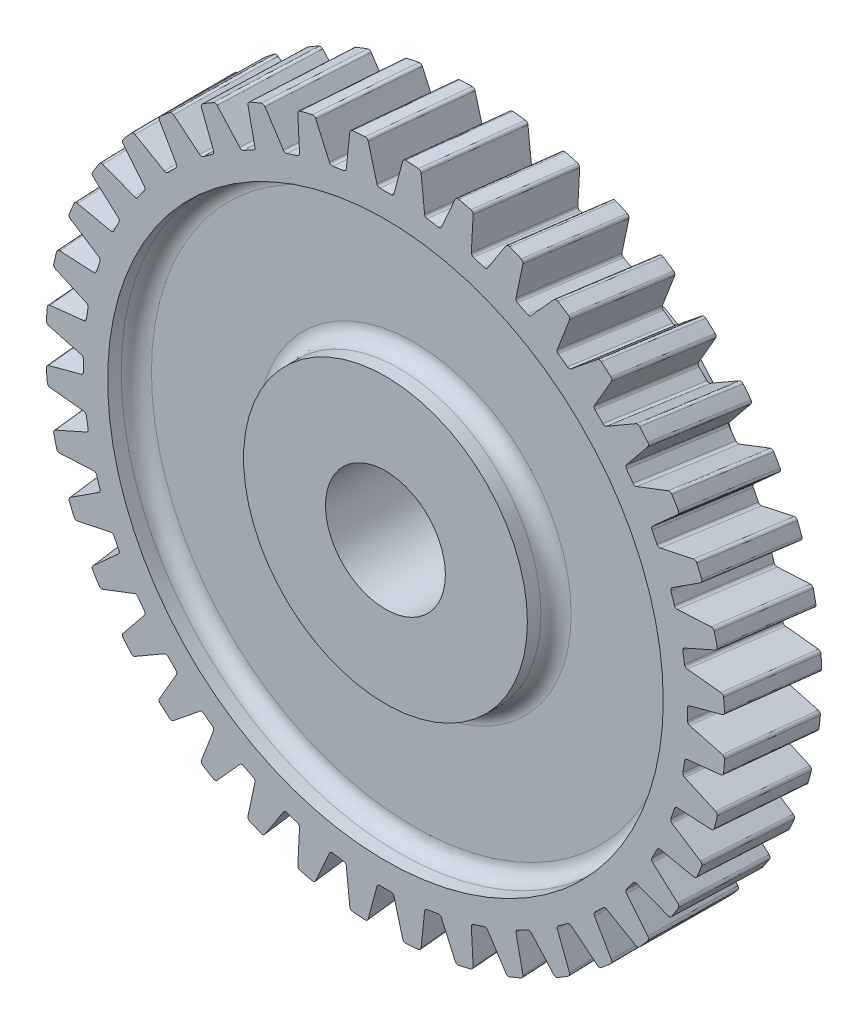
SolidWorks part; units mm, degrees
ref_plane "Front Plane" through (0, 0, 0) normal (0, 0, 1) x (1, 0, 0)
ref_plane "Top Plane" through (0, 0, 0) normal (0, 1, 0) x (1, 0, 0)
ref_plane "Right Plane" through (0, 0, 0) normal (1, 0, 0) x (0, 0, -1)
sketch "Sketch2" plane through (0, 0, 0) normal (1, 0, 0) x (0, 0, -1)
  line L0 (0, 0) -> (0, 22.5) construction
  line L1 (11, 3.9688) -> (-3.2, 3.9687)
  line L2 (-3.2, 3.9687) -> (-3.2, 9.4)
  line L3 (-3.2, 9.4) -> (-1.3, 9.4)
  line L4 (-1.3, 9.4) -> (-1.3, 18.4)
  line L5 (-1.3, 18.4) -> (-3.2, 18.4)
  line L6 (-3.2, 18.4) -> (-3.2, 22.5)
  line L7 (-3.2, 22.5) -> (3.2, 22.5)
  line L8 (3.2, 18.4) -> (3.2, 22.5)
  line L9 (1.3, 18.4) -> (3.2, 18.4)
  line L10 (1.3, 9.4) -> (1.3, 18.4)
  line L11 (3.2, 9.4) -> (1.3, 9.4)
  line L12 (3.2, 9.4) -> (11, 9.4)
  line L13 (11, 9.4) -> (11, 3.9688)
  line L14 (0, 0) -> (14.174, 0) construction
  dimension "D1" = 14.2
  dimension "D2" = 3.2
  dimension "D3" = 4.5
  dimension "D4" = 7.9375
  dimension "D5" = 9.4
  dimension "D6" = 9
  dimension "D7" = 22.5
  dimension "D8" = 6.4
revolve "Revolve1" add sketch "Sketch2" angle 360 about L14
fillet "Fillet1" radius 1 4 edges at (18.4, 0, 1.3) (9.4, 0, 1.3) (9.4, 0, -1.3) (18.4, 0, -1.3)
sketch "Sketch3" plane through (0, 0, 3.2) normal (0, 0, 1) x (1, 0, 0)
  line L0 (0, 22.6922) -> (0, 20) construction
  line L1 (-0.525, 20) -> (0.525, 20)
  line L2 (0.525, 20) -> (1.2464, 22.6922)
  line L3 (1.2464, 22.6922) -> (-1.2464, 22.6922)
  line L4 (-0.525, 20) -> (-1.2464, 22.6922)
  dimension "D1" = 20
  dimension "D2" = 1.05
  dimension "D3" = 15
  dimension "D4" = 2.4927
sketch "Sketch4" plane through (0, 0, 0) normal (0, 1, 0) x (1, 0, 0)
  line L0 (0, -3.2) -> (0.691, 3.2)
  line L1 (1.2464, -3.2) -> (-1.2464, -3.2) construction
  line L2 (22.5, 3.2) -> (-22.5, 3.2) construction
  dimension "D1" = 6.4372
sweep "Cut-Sweep1" cut profiles "Sketch3" path "Sketch4"
pattern_circular "CirPattern1" count 40 over 360 about axis through (0, 0, 3.2) along (0, 0, 1) of "Cut-Sweep1"
fillet "Fillet2" radius 0.2 160 edges at (1.526, 22.4482, 0.0047) (0.8705, 20, 0) (-0.8445, 22.4841, -0.0056) (-2.0045, 22.4105, 0.0047) (-2.2689, 19.8899, 0) (-3.306, 19.7257, 0) (-4.3514, 22.0752, -0.0056) (-5.4856, 21.8211, 0.0047) (-5.3525, 19.2901, 0) (-6.3511, 18.9657, 0) (-7.7512, 21.1227, -0.0056) (-8.8316, 20.6943, 0.0047) (-8.3042, 18.2153, 0) (-9.2398, 17.7386, 0) (-10.9601, 19.6501, -0.0056) (-11.9602, 19.0579, 0.0047) (-11.0515, 16.692, 0) (-11.9009, 16.0748, 0) (-13.8991, 17.6936, -0.0056) (-14.7943, 16.9523, 0.0047) (-13.5266, 14.7577, 0) (-14.2691, 14.0152, 0) (-16.4959, 15.3015, -0.0056) (-17.264, 14.4292, 0.0047) (-15.6687, 12.4599, 0) (-16.2859, 11.6105, 0) (-18.6865, 12.5326, -0.0056) (-19.3087, 11.5509, 0.0047) (-17.4249, 9.8554, 0) (-17.9016, 8.9199, 0) (-20.4169, 9.4551, -0.0056) (-20.878, 8.3882, 0.0047) (-18.7521, 7.0082, 0) (-19.0766, 6.0096, 0) (-21.6447, 6.1448, -0.0056) (-21.9331, 5.0188, 0.0047) (-19.6176, 3.9885, 0) (-19.7818, 2.9514, 0) (-22.3394, 2.6832, -0.0056) (-22.4482, 1.526, 0.0047) (-20, 0.8705, 0) (-20, -0.1795, 0) (-22.4841, -0.8445, -0.0056) (-22.4105, -2.0045, 0.0047) (-19.8899, -2.2689, 0) (-19.7257, -3.306, 0) (-22.0752, -4.3514, -0.0056) (-21.8211, -5.4856, 0.0047) (-19.2901, -5.3525, 0) (-18.9657, -6.3511, 0) (-21.1227, -7.7512, -0.0056) (-20.6943, -8.8316, 0.0047) (-18.2153, -8.3042, 0) (-17.7386, -9.2398, 0) (-19.6501, -10.9601, -0.0056) (-19.0579, -11.9602, 0.0047) (-16.692, -11.0515, 0) (-16.0748, -11.9009, 0) (-17.6936, -13.8991, -0.0056) (-16.9523, -14.7943, 0.0047) (-14.7577, -13.5266, 0) (-14.0152, -14.2691, 0) (-15.3015, -16.4959, -0.0056) (-14.4292, -17.264, 0.0047) (-12.4599, -15.6687, 0) (-11.6105, -16.2859, 0) (-12.5326, -18.6865, -0.0056) (-11.5509, -19.3087, 0.0047) (-9.8554, -17.4249, 0) (-8.9199, -17.9016, 0) (-9.4551, -20.4169, -0.0056) (-8.3882, -20.878, 0.0047) (-7.0082, -18.7521, 0) (-6.0096, -19.0766, 0) (-6.1448, -21.6447, -0.0056) (-5.0188, -21.9331, 0.0047) (-3.9885, -19.6176, 0) (-2.9514, -19.7818, 0) (-2.6832, -22.3394, -0.0056) (-1.526, -22.4482, 0.0047) (-0.8705, -20, 0) (0.1795, -20, 0) (0.8445, -22.4841, -0.0056) (2.0045, -22.4105, 0.0047) (2.2689, -19.8899, 0) (3.306, -19.7257, 0) (4.3514, -22.0752, -0.0056) (5.4856, -21.8211, 0.0047) (5.3525, -19.2901, 0) (6.3511, -18.9657, 0) (7.7512, -21.1227, -0.0056) (8.8316, -20.6943, 0.0047) (8.3042, -18.2153, 0) (9.2398, -17.7386, 0) (10.9601, -19.6501, -0.0056) (11.9602, -19.0579, 0.0047) (11.0515, -16.692, 0) (11.9009, -16.0748, 0) (13.8991, -17.6936, -0.0056) (14.7943, -16.9523, 0.0047) (13.5266, -14.7577, 0) (14.2691, -14.0152, 0) (16.4959, -15.3015, -0.0056) (17.264, -14.4292, 0.0047) (15.6687, -12.4599, 0) (16.2859, -11.6105, 0) (18.6865, -12.5326, -0.0056) (19.3087, -11.5509, 0.0047) (17.4249, -9.8554, 0) (17.9016, -8.9199, 0) (20.4169, -9.4551, -0.0056) (20.878, -8.3882, 0.0047) (18.7521, -7.0082, 0) (19.0766, -6.0096, 0) (21.6447, -6.1448, -0.0056) (21.9331, -5.0188, 0.0047) (19.6176, -3.9885, 0) (19.7818, -2.9514, 0) (22.3394, -2.6832, -0.0056) (22.4482, -1.526, 0.0047) (20, -0.8705, 0) (20, 0.1795, 0) (22.4841, 0.8445, -0.0056) (22.4105, 2.0045, 0.0047) (19.8899, 2.2689, 0) (19.7257, 3.306, 0) (22.0752, 4.3514, -0.0056) (21.8211, 5.4856, 0.0047) (19.2901, 5.3525, 0) (18.9657, 6.3511, 0) (21.1227, 7.7512, -0.0056) (20.6943, 8.8316, 0.0047) (18.2153, 8.3042, 0) (17.7386, 9.2398, 0) (19.6501, 10.9601, -0.0056) (19.0579, 11.9602, 0.0047) (16.692, 11.0515, 0) (16.0748, 11.9009, 0) (17.6936, 13.8991, -0.0056) (16.9523, 14.7943, 0.0047) (14.7577, 13.5266, 0) (14.0152, 14.2691, 0) (15.3015, 16.4959, -0.0056) (14.4292, 17.264, 0.0047) (12.4599, 15.6687, 0) (11.6105, 16.2859, 0) (12.5326, 18.6865, -0.0056) (11.5509, 19.3087, 0.0047) (9.8554, 17.4249, 0) (8.9199, 17.9016, 0) (9.4551, 20.4169, -0.0056) (8.3882, 20.878, 0.0047) (7.0082, 18.7521, 0) (6.0096, 19.0766, 0) (6.1448, 21.6447, -0.0056) (5.0188, 21.9331, 0.0047) (3.9885, 19.6176, 0) (2.9514, 19.7818, 0) (2.6832, 22.3394, -0.0056) (-0.1795, 20, 0)
ref_axis "gear axis" through (0, 0, -11) along (0, 0, 1)
ref_plane "Plane1" through (9.4, 0, 0) normal (1, 0, 0) x (0, 0, -1)
sketch "Sketch7" plane through (9.4, 0, 0) normal (1, 0, 0) x (0, 0, -1)
  line L0 (11, 0) -> (-3.2, 0) construction
  line L1 (11, -9.4) -> (11, 9.4) construction
  circle A0 centre (7, 0) radius 1.25
  dimension "D1" = 2.5
  dimension "D2" = 4
extrude "Cut-Extrude1" cut sketch "Sketch7" against normal through all
